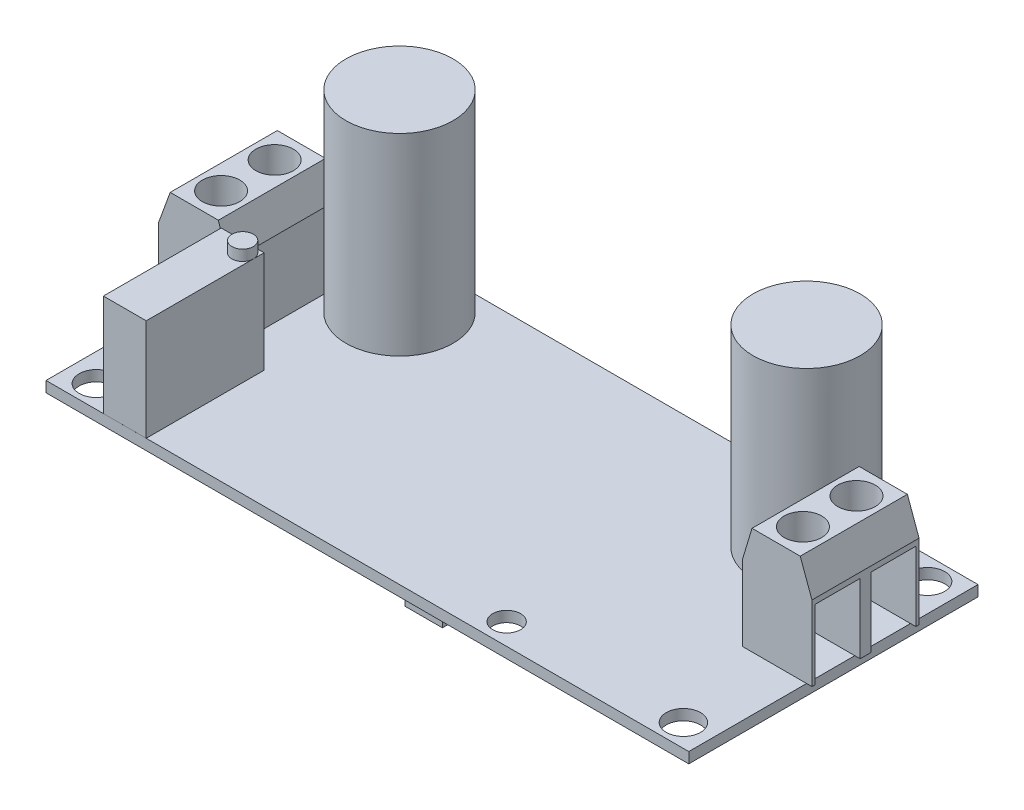
SolidWorks part; units mm, degrees
ref_plane "Front Plane" through (0, 0, 0) normal (0, 0, 1) x (1, 0, 0)
ref_plane "Top Plane" through (0, 0, 0) normal (0, 1, 0) x (1, 0, 0)
ref_plane "Right Plane" through (0, 0, 0) normal (1, 0, 0) x (0, 0, -1)
sketch "Sketch1" plane through (0, 0, 0) normal (0, 1, 0) x (1, 0, 0)
  line L1 (-23.5313, 9.2026) -> (36.4687, 9.2026)
  line L2 (-23.5313, 9.2026) -> (-23.5313, -17.7974)
  line L3 (-23.5313, -17.7974) -> (36.4687, -17.7974)
  line L4 (36.4687, 9.2026) -> (36.4687, -17.7974)
  dimension "D1" = 60
  dimension "D2" = 26
extrude "Boss-Extrude1" add sketch "Sketch1" along normal blind 1
ref_plane "Plane1" through (6.4687, 0, 0) normal (-1, 0, 0) x (0, 0, 1)
ref_plane "Plane2" through (0, 0, 4.2974) normal (0, 0, 1) x (1, 0, 0)
sketch "Sketch5" plane through (0, 1, 0) normal (0, 1, 0) x (1, 0, 0)
  line L0 (36.4687, 9.2026) -> (-23.5313, 9.2026) construction
  line L1 (-23.5313, 9.2026) -> (-23.5313, -17.7974) construction
  circle A0 centre (-12.5313, 4.2026) radius 5
  dimension "D1" = 10
  dimension "D2" = 5
  dimension "D3" = 11
extrude "Boss-Extrude2" add sketch "Sketch5" along normal blind 18
mirror "Mirror1" about plane through (6.4687, 0, 0) normal (-1, 0, 0) of "Boss-Extrude2"
ref_plane "Plane3" through (0, 0, -3.2026) normal (0, 0, 1) x (1, 0, 0)
ref_axis "Axis1" through (-23.5313, 1, -3.2026) along (1, 0, 0)
ref_plane "Plane4" through (36.4687, 0, 0) normal (1, 0, 0) x (0, 0, -1)
ref_point "Point3"
ref_axis "Axis2" through (36.4687, -0.05, -3.2026) along (0, 1, 0)
sketch "Sketch8" plane through (0, 0, -3.2026) normal (0, 0, 1) x (1, 0, 0)
  line L0 (-23.5313, 1) -> (36.4687, 1) construction
  line L1 (30.4687, 1) -> (36.9687, 1)
  line L2 (30.4687, 1) -> (30.4687, 8)
  line L4 (36.9687, 1) -> (36.9687, 8)
  line L6 (36.4687, -0.05) -> (36.4687, 1.05) construction
  line L7 (36.9687, 8) -> (35.8758, 11)
  line L8 (35.8758, 11) -> (31.3758, 11)
  line L9 (31.3758, 11) -> (30.4687, 8)
  dimension "D1" = 6.5
  dimension "D2" = 0.5
  dimension "D3" = 7
  dimension "D4" = 4.5
  dimension "D5" = 3
extrude "Boss-Extrude3" add sketch "Sketch8" along normal blind 5
sketch "Sketch9" plane through (0, 11, 0) normal (0, 1, 0) x (1, 0, 0)
  line L0 (35.8758, 3.2026) -> (31.3758, 3.2026) construction
  line L2 (31.3758, -1.7974) -> (31.3758, 3.2026) construction
  circle A0 centre (33.6258, 0.7026) radius 1.75
  dimension "D1" = 3.5
  dimension "D2" = 2.5
  dimension "D3" = 2.25
extrude "Cut-Extrude1" cut sketch "Sketch9" against normal blind 5
sketch "Sketch10" plane through (36.9687, 0, 0) normal (1, 0, 0) x (0, 0, -1)
  line L0 (-1.7974, 1) -> (3.2026, 1) construction
  line L1 (2.9026, 1) -> (-1.2974, 1)
  line L2 (2.9026, 1) -> (2.9026, 7.5)
  line L3 (2.9026, 7.5) -> (-1.2974, 7.5)
  line L4 (-1.2974, 1) -> (-1.2974, 7.5)
  line L5 (-1.7974, 8) -> (3.2026, 8) construction
  line L6 (-1.7974, 1) -> (-1.7974, 8) construction
  line L7 (3.2026, 0.55) -> (3.2026, -0.55) construction
  dimension "D1" = 0.5
  dimension "D2" = 0.5
  dimension "D3" = 0.3
extrude "Cut-Extrude2" cut sketch "Sketch10" against normal blind 5
ref_plane "Plane5" through (0, 0, 1.7974) normal (0, 0, 1) x (1, 0, 0)
mirror "Mirror3" about plane through (0, 0, 1.7974) normal (0, 0, 1) of "Cut-Extrude2", "Cut-Extrude1", "Boss-Extrude3"
mirror "Mirror4" about plane through (6.4687, 0, 0) normal (-1, 0, 0) of "Mirror3", "Cut-Extrude2", "Cut-Extrude1", "Boss-Extrude3"
sketch "Sketch11" plane through (0, 1, 0) normal (0, 1, 0) x (1, 0, 0)
  line L0 (36.4687, 9.2026) -> (25.4687, 9.2026) construction
  line L1 (36.4687, -0.55) -> (36.4687, 0.55) construction
  circle A0 centre (33.8687, 7.1026) radius 1.6
  dimension "D1" = 3.2
  dimension "D2" = 2.1
  dimension "D3" = 2.6
extrude "Cut-Extrude3" cut sketch "Sketch11" against normal up to next
mirror "Mirror5" about plane through (0, 0, 4.2974) normal (0, 0, 1) of "Cut-Extrude3"
mirror "Mirror6" about plane through (6.4687, 0, 0) normal (-1, 0, 0) of "Mirror5", "Cut-Extrude3"
sketch "Sketch12" plane through (0, 1, 0) normal (0, 1, 0) x (1, 0, 0)
  line L0 (-17.5313, -6.7974) -> (-23.5313, -6.7974) construction
  line L1 (-18.1764, -6.7974) -> (-14.1764, -6.7974)
  line L2 (-18.1764, -6.7974) -> (-18.1764, -17.7964)
  line L3 (-18.1764, -17.7964) -> (-14.1764, -17.7964)
  line L4 (-14.1764, -6.7974) -> (-14.1764, -17.7964)
  dimension "D1" = 4
  dimension "D2" = 10.999
extrude "Boss-Extrude4" add sketch "Sketch12" along normal blind 9.5
sketch "Sketch13" plane through (0, 10.5, 0) normal (0, 1, 0) x (1, 0, 0)
  line L0 (-14.1764, -6.7974) -> (-18.1764, -6.7974) construction
  line L1 (-14.1764, -17.7964) -> (-14.1764, -6.7974) construction
  circle A0 centre (-15.1764, -7.7974) radius 1
  dimension "D1" = 2
  dimension "D2" = 1
  dimension "D3" = 1
extrude "Boss-Extrude5" add sketch "Sketch13" along normal blind 1
sketch "Sketch15" plane through (0, 1, 0) normal (0, 1, 0) x (1, 0, 0)
  line L0 (-23.5313, -17.7974) -> (36.4687, -17.7974) construction
  line L1 (36.4687, -0.55) -> (36.4687, 0.55) construction
  circle A0 centre (17.4687, -15.7974) radius 1.3
  dimension "D1" = 2
  dimension "D2" = 2.6
  dimension "D3" = 19
extrude "Cut-Extrude4" cut sketch "Sketch15" against normal up to next
sketch "Sketch16" plane through (0, 0, 0) normal (0, -1, 0) x (1, 0, 0)
  line L0 (-23.5313, 17.7974) -> (36.4687, 17.7974) construction
  line L1 (-11.5313, 11.2974) -> (-1.5313, 11.2974)
  line L2 (-11.5313, 11.2974) -> (-11.5313, 7.7974)
  line L3 (-11.5313, 7.7974) -> (-1.5313, 7.7974)
  line L4 (-1.5313, 11.2974) -> (-1.5313, 7.7974)
  line L5 (-23.5313, -9.2026) -> (-23.5313, 17.7974) construction
  dimension "D1" = 6.5
  dimension "D2" = 12
  dimension "D3" = 10
  dimension "D4" = 3.5
extrude "Boss-Extrude6" add sketch "Sketch16" along normal blind 1
ref_plane "Plane6" through (-11.3313, 0, 0) normal (-1, 0, 0) x (0, 0, 1)
sketch "Sketch17" plane through (-11.3313, 0, 0) normal (-1, 0, 0) x (0, 0, 1)
  line L0 (11.2974, -0.7344) -> (11.6534, -0.7344)
  line L1 (11.2974, -1) -> (11.2974, 0) construction
  line L2 (11.6534, -0.7344) -> (11.6534, -0.1197)
  line L3 (11.6534, -0.1197) -> (12.7974, -0.1197)
  line L4 (12.7974, -0.1197) -> (12.7974, 0)
  line L5 (-9.2026, 0) -> (17.7974, 0) construction
  line L6 (12.7974, 0) -> (11.5334, 0)
  line L7 (11.5334, 0) -> (11.5334, -0.6177)
  line L8 (11.5334, -0.6177) -> (11.2974, -0.6177)
  line L9 (11.2974, -0.6177) -> (11.2974, -0.7344)
  point P4 (12.7974, -0.0598)
  dimension "D1" = 1.5
extrude "Boss-Extrude7" add sketch "Sketch17" against normal blind 0.4
pattern_linear "LPattern1" count 8 spacing 1.3 along (1, 0, 0) of "Boss-Extrude7"
ref_plane "Plane9" through (0, 0, 9.5474) normal (0, 0, -1) x (-1, 0, 0)
mirror "Mirror7" about plane through (0, 0, 9.5474) normal (0, 0, -1) of "LPattern1", "Boss-Extrude7"
sketch "Sketch18" plane through (0, 0, 0) normal (0, -1, 0) x (1, 0, 0)
  line L0 (36.4687, -9.2026) -> (-23.5313, -9.2026) construction
  line L1 (-16.5313, -3.7026) -> (-14.0313, -3.7026)
  line L2 (-16.5313, -3.7026) -> (-16.5313, -7.2026)
  line L3 (-16.5313, -7.2026) -> (-14.0313, -7.2026)
  line L4 (-14.0313, -3.7026) -> (-14.0313, -7.2026)
  line L5 (-23.5313, -9.2026) -> (-23.5313, 17.7974) construction
  dimension "D1" = 2
  dimension "D2" = 5.5
  dimension "D3" = 7
  dimension "D4" = 9.5
extrude "Boss-Extrude8" add sketch "Sketch18" along normal blind 2
sketch "Sketch19" plane through (0, 0, 0) normal (0, -1, 0) x (1, 0, 0)
  line L0 (-23.5313, 17.7974) -> (36.4687, 17.7974) construction
  line L1 (8.4687, 16.2974) -> (11.9687, 16.2974)
  line L2 (8.4687, 16.2974) -> (8.4687, 13.7974)
  line L3 (8.4687, 13.7974) -> (11.9687, 13.7974)
  line L4 (11.9687, 16.2974) -> (11.9687, 13.7974)
  line L5 (36.4687, -0.55) -> (36.4687, 0.55) construction
  dimension "D1" = 1.5
  dimension "D2" = 24.5
  dimension "D3" = 3.5
  dimension "D4" = 2.5
extrude "Boss-Extrude9" add sketch "Sketch19" along normal blind 2
